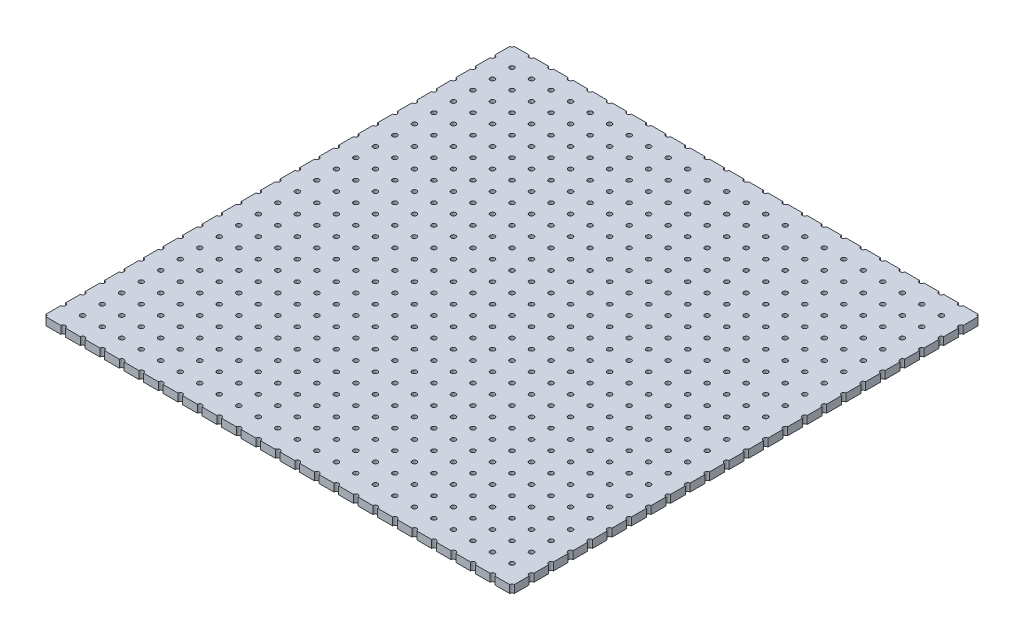
SolidWorks part; units mm, degrees
ref_plane "Front Plane" through (0, 0, 0) normal (0, 0, 1) x (1, 0, 0)
ref_plane "Top Plane" through (0, 0, 0) normal (0, 1, 0) x (1, 0, 0)
ref_plane "Right Plane" through (0, 0, 0) normal (1, 0, 0) x (0, 0, -1)
sketch "Sketch1" plane through (0, 0, 0) normal (0, 1, 0) x (1, 0, 0)
  line L0 (0, 28) -> (0, 47)
  line L1 (3, 0) -> (22, 0)
  line L2 (0, 3) -> (0, 22)
  line L3 (3, 300) -> (22, 300)
  line L4 (300, 3) -> (300, 22)
  line L5 (28, 0) -> (47, 0)
  line L6 (53, 0) -> (72, 0)
  line L7 (78, 0) -> (97, 0)
  line L8 (103, 0) -> (122, 0)
  line L9 (128, 0) -> (147, 0)
  line L10 (153, 0) -> (172, 0)
  line L11 (178, 0) -> (197, 0)
  line L12 (203, 0) -> (222, 0)
  line L13 (228, 0) -> (247, 0)
  line L14 (253, 0) -> (272, 0)
  line L15 (278, 0) -> (297, 0)
  line L16 (300, 28) -> (300, 47)
  line L17 (300, 53) -> (300, 72)
  line L18 (300, 78) -> (300, 97)
  line L19 (300, 103) -> (300, 122)
  line L20 (300, 128) -> (300, 147)
  line L21 (300, 153) -> (300, 172)
  line L22 (300, 178) -> (300, 197)
  line L23 (300, 203) -> (300, 222)
  line L24 (300, 228) -> (300, 247)
  line L25 (300, 253) -> (300, 272)
  line L26 (300, 278) -> (300, 297)
  line L27 (278, 300) -> (297, 300)
  line L28 (253, 300) -> (272, 300)
  line L29 (228, 300) -> (247, 300)
  line L30 (203, 300) -> (222, 300)
  line L31 (178, 300) -> (197, 300)
  line L32 (153, 300) -> (172, 300)
  line L33 (128, 300) -> (147, 300)
  line L34 (103, 300) -> (122, 300)
  line L35 (78, 300) -> (97, 300)
  line L36 (53, 300) -> (72, 300)
  line L37 (28, 300) -> (47, 300)
  line L38 (0, 278) -> (0, 297)
  line L39 (0, 253) -> (0, 272)
  line L40 (0, 228) -> (0, 247)
  line L41 (0, 203) -> (0, 222)
  line L42 (0, 178) -> (0, 197)
  line L43 (0, 153) -> (0, 172)
  line L44 (0, 103) -> (0, 122)
  line L45 (0, 128) -> (0, 147)
  line L46 (0, 78) -> (0, 97)
  line L47 (0, 53) -> (0, 72)
  arc A11 (300, 28) -> (300, 22) centre (300, 25) ccw
  arc A23 (0, 22) -> (0, 28) centre (0, 25) ccw
  arc A24 (0, 47) -> (0, 53) centre (0, 50) ccw
  arc A36 (300, 53) -> (300, 47) centre (300, 50) ccw
  arc A37 (0, 72) -> (0, 78) centre (0, 75) ccw
  arc A49 (300, 78) -> (300, 72) centre (300, 75) ccw
  arc A50 (0, 97) -> (0, 103) centre (0, 100) ccw
  arc A62 (300, 103) -> (300, 97) centre (300, 100) ccw
  arc A63 (0, 122) -> (0, 128) centre (0, 125) ccw
  arc A75 (300, 128) -> (300, 122) centre (300, 125) ccw
  arc A76 (0, 147) -> (0, 153) centre (0, 150) ccw
  arc A88 (300, 153) -> (300, 147) centre (300, 150) ccw
  arc A89 (0, 172) -> (0, 178) centre (0, 175) ccw
  arc A101 (300, 178) -> (300, 172) centre (300, 175) ccw
  arc A102 (0, 197) -> (0, 203) centre (0, 200) ccw
  arc A114 (300, 203) -> (300, 197) centre (300, 200) ccw
  arc A115 (0, 222) -> (0, 228) centre (0, 225) ccw
  arc A127 (300, 228) -> (300, 222) centre (300, 225) ccw
  arc A128 (0, 247) -> (0, 253) centre (0, 250) ccw
  arc A140 (300, 253) -> (300, 247) centre (300, 250) ccw
  arc A141 (0, 272) -> (0, 278) centre (0, 275) ccw
  arc A153 (300, 278) -> (300, 272) centre (300, 275) ccw
  arc A154 (0, 297) -> (3, 300) centre (0, 300) ccw
  arc A155 (22, 300) -> (28, 300) centre (25, 300) ccw
  arc A156 (47, 300) -> (53, 300) centre (50, 300) ccw
  arc A157 (72, 300) -> (78, 300) centre (75, 300) ccw
  arc A158 (97, 300) -> (103, 300) centre (100, 300) ccw
  arc A159 (122, 300) -> (128, 300) centre (125, 300) ccw
  arc A160 (147, 300) -> (153, 300) centre (150, 300) ccw
  arc A161 (172, 300) -> (178, 300) centre (175, 300) ccw
  arc A162 (197, 300) -> (203, 300) centre (200, 300) ccw
  arc A163 (222, 300) -> (228, 300) centre (225, 300) ccw
  arc A164 (247, 300) -> (253, 300) centre (250, 300) ccw
  arc A165 (272, 300) -> (278, 300) centre (275, 300) ccw
  arc A166 (297, 300) -> (300, 297) centre (300, 300) ccw
  circle A168 centre (25, 25) radius 3
  circle A169 centre (50, 25) radius 3
  circle A170 centre (75, 25) radius 3
  circle A171 centre (100, 25) radius 3
  circle A172 centre (125, 25) radius 3
  circle A173 centre (150, 25) radius 3
  circle A174 centre (175, 25) radius 3
  circle A175 centre (200, 25) radius 3
  circle A176 centre (225, 25) radius 3
  circle A177 centre (250, 25) radius 3
  circle A178 centre (275, 25) radius 3
  circle A181 centre (25, 50) radius 3
  circle A182 centre (50, 50) radius 3
  circle A183 centre (75, 50) radius 3
  circle A184 centre (100, 50) radius 3
  circle A185 centre (125, 50) radius 3
  circle A186 centre (150, 50) radius 3
  circle A187 centre (175, 50) radius 3
  circle A188 centre (200, 50) radius 3
  circle A189 centre (225, 50) radius 3
  circle A190 centre (250, 50) radius 3
  circle A191 centre (275, 50) radius 3
  circle A194 centre (25, 75) radius 3
  circle A195 centre (50, 75) radius 3
  circle A196 centre (75, 75) radius 3
  circle A197 centre (100, 75) radius 3
  circle A198 centre (125, 75) radius 3
  circle A199 centre (150, 75) radius 3
  circle A200 centre (175, 75) radius 3
  circle A201 centre (200, 75) radius 3
  circle A202 centre (225, 75) radius 3
  circle A203 centre (250, 75) radius 3
  circle A204 centre (275, 75) radius 3
  circle A207 centre (25, 100) radius 3
  circle A208 centre (50, 100) radius 3
  circle A209 centre (75, 100) radius 3
  circle A210 centre (100, 100) radius 3
  circle A211 centre (125, 100) radius 3
  circle A212 centre (150, 100) radius 3
  circle A213 centre (175, 100) radius 3
  circle A214 centre (200, 100) radius 3
  circle A215 centre (225, 100) radius 3
  circle A216 centre (250, 100) radius 3
  circle A217 centre (275, 100) radius 3
  circle A220 centre (25, 125) radius 3
  circle A221 centre (50, 125) radius 3
  circle A222 centre (75, 125) radius 3
  circle A223 centre (100, 125) radius 3
  circle A224 centre (125, 125) radius 3
  circle A225 centre (150, 125) radius 3
  circle A226 centre (175, 125) radius 3
  circle A227 centre (200, 125) radius 3
  circle A228 centre (225, 125) radius 3
  circle A229 centre (250, 125) radius 3
  circle A230 centre (275, 125) radius 3
  circle A233 centre (25, 150) radius 3
  circle A234 centre (50, 150) radius 3
  circle A235 centre (75, 150) radius 3
  circle A236 centre (100, 150) radius 3
  circle A237 centre (125, 150) radius 3
  circle A238 centre (150, 150) radius 3
  circle A239 centre (175, 150) radius 3
  circle A240 centre (200, 150) radius 3
  circle A241 centre (225, 150) radius 3
  circle A242 centre (250, 150) radius 3
  circle A243 centre (275, 150) radius 3
  circle A246 centre (25, 175) radius 3
  circle A247 centre (50, 175) radius 3
  circle A248 centre (75, 175) radius 3
  circle A249 centre (100, 175) radius 3
  circle A250 centre (125, 175) radius 3
  circle A251 centre (150, 175) radius 3
  circle A252 centre (175, 175) radius 3
  circle A253 centre (200, 175) radius 3
  circle A254 centre (225, 175) radius 3
  circle A255 centre (250, 175) radius 3
  circle A256 centre (275, 175) radius 3
  circle A259 centre (25, 200) radius 3
  circle A260 centre (50, 200) radius 3
  circle A261 centre (75, 200) radius 3
  circle A262 centre (100, 200) radius 3
  circle A263 centre (125, 200) radius 3
  circle A264 centre (150, 200) radius 3
  circle A265 centre (175, 200) radius 3
  circle A266 centre (200, 200) radius 3
  circle A267 centre (225, 200) radius 3
  circle A268 centre (250, 200) radius 3
  circle A269 centre (275, 200) radius 3
  circle A272 centre (25, 225) radius 3
  circle A273 centre (50, 225) radius 3
  circle A274 centre (75, 225) radius 3
  circle A275 centre (100, 225) radius 3
  circle A276 centre (125, 225) radius 3
  circle A277 centre (150, 225) radius 3
  circle A278 centre (175, 225) radius 3
  circle A279 centre (200, 225) radius 3
  circle A280 centre (225, 225) radius 3
  circle A281 centre (250, 225) radius 3
  circle A282 centre (275, 225) radius 3
  circle A285 centre (25, 250) radius 3
  circle A286 centre (50, 250) radius 3
  circle A287 centre (75, 250) radius 3
  circle A288 centre (100, 250) radius 3
  circle A289 centre (125, 250) radius 3
  circle A290 centre (150, 250) radius 3
  circle A291 centre (175, 250) radius 3
  circle A292 centre (200, 250) radius 3
  circle A293 centre (225, 250) radius 3
  circle A294 centre (250, 250) radius 3
  circle A295 centre (275, 250) radius 3
  circle A298 centre (25, 275) radius 3
  circle A299 centre (50, 275) radius 3
  circle A300 centre (75, 275) radius 3
  circle A301 centre (100, 275) radius 3
  circle A302 centre (125, 275) radius 3
  circle A303 centre (150, 275) radius 3
  circle A304 centre (175, 275) radius 3
  circle A305 centre (200, 275) radius 3
  circle A306 centre (225, 275) radius 3
  circle A307 centre (250, 275) radius 3
  circle A308 centre (275, 275) radius 3
  arc A310 (3, 0) -> (0, 3) centre (0, 0) ccw
  arc A311 (28, 0) -> (22, 0) centre (25, 0) ccw
  arc A312 (53, 0) -> (47, 0) centre (50, 0) ccw
  arc A313 (78, 0) -> (72, 0) centre (75, 0) ccw
  arc A314 (103, 0) -> (97, 0) centre (100, 0) ccw
  arc A315 (128, 0) -> (122, 0) centre (125, 0) ccw
  arc A316 (153, 0) -> (147, 0) centre (150, 0) ccw
  arc A317 (178, 0) -> (172, 0) centre (175, 0) ccw
  arc A318 (203, 0) -> (197, 0) centre (200, 0) ccw
  arc A319 (228, 0) -> (222, 0) centre (225, 0) ccw
  arc A320 (253, 0) -> (247, 0) centre (250, 0) ccw
  arc A321 (278, 0) -> (272, 0) centre (275, 0) ccw
  arc A322 (300, 3) -> (297, 0) centre (300, 0) ccw
  arc A324 (302.8689, 25.8771) -> (300, 22) centre (300, 25) ccw [skipped]
  arc A325 (0, 22) -> (0, 28) centre (0, 25) ccw [skipped]
  arc A326 (0, 47) -> (0, 53) centre (0, 50) ccw [skipped]
  arc A327 (300, 53) -> (300, 47) centre (300, 50) ccw [skipped]
  arc A328 (0, 72) -> (0, 78) centre (0, 75) ccw [skipped]
  arc A329 (300, 78) -> (300, 72) centre (300, 75) ccw [skipped]
  arc A330 (0, 97) -> (0, 103) centre (0, 100) ccw [skipped]
  arc A331 (300, 103) -> (300, 97) centre (300, 100) ccw [skipped]
  arc A332 (0, 122) -> (0, 128) centre (0, 125) ccw [skipped]
  arc A333 (300, 128) -> (300, 122) centre (300, 125) ccw [skipped]
  arc A334 (0, 147) -> (0, 153) centre (0, 150) ccw [skipped]
  arc A335 (300, 153) -> (300, 147) centre (300, 150) ccw [skipped]
  arc A336 (0, 172) -> (0, 178) centre (0, 175) ccw [skipped]
  arc A337 (300, 178) -> (300, 172) centre (300, 175) ccw [skipped]
  arc A338 (0, 197) -> (0, 203) centre (0, 200) ccw [skipped]
  arc A339 (300, 203) -> (300, 197) centre (300, 200) ccw [skipped]
  arc A340 (0, 222) -> (0, 228) centre (0, 225) ccw [skipped]
  arc A341 (300, 228) -> (300, 222) centre (300, 225) ccw [skipped]
  arc A342 (0, 247) -> (0, 253) centre (0, 250) ccw [skipped]
  arc A343 (300, 253) -> (300, 247) centre (300, 250) ccw [skipped]
  arc A344 (0, 272) -> (0, 278) centre (0, 275) ccw [skipped]
  arc A345 (300, 278) -> (300, 272) centre (300, 275) ccw [skipped]
  dimension "D8" = 12
  dimension "D9" = 2
extrude "Boss-Extrude1" add sketch "Sketch1" along normal blind 10
mirror "Mirror1" about plane through (300, 10, -178) normal (-1, 0, 0) of "Boss-Extrude1"
ref_plane "Plane2" through (0, 0, -300) normal (0, 0, -1) x (-1, 0, 0)
mirror "Mirror6" about plane through (0, 0, -300) normal (0, 0, -1) of "Boss-Extrude1"
mirror "Mirror7" about plane through (300, 10, -522) normal (1, 0, 0) of "Mirror6"
